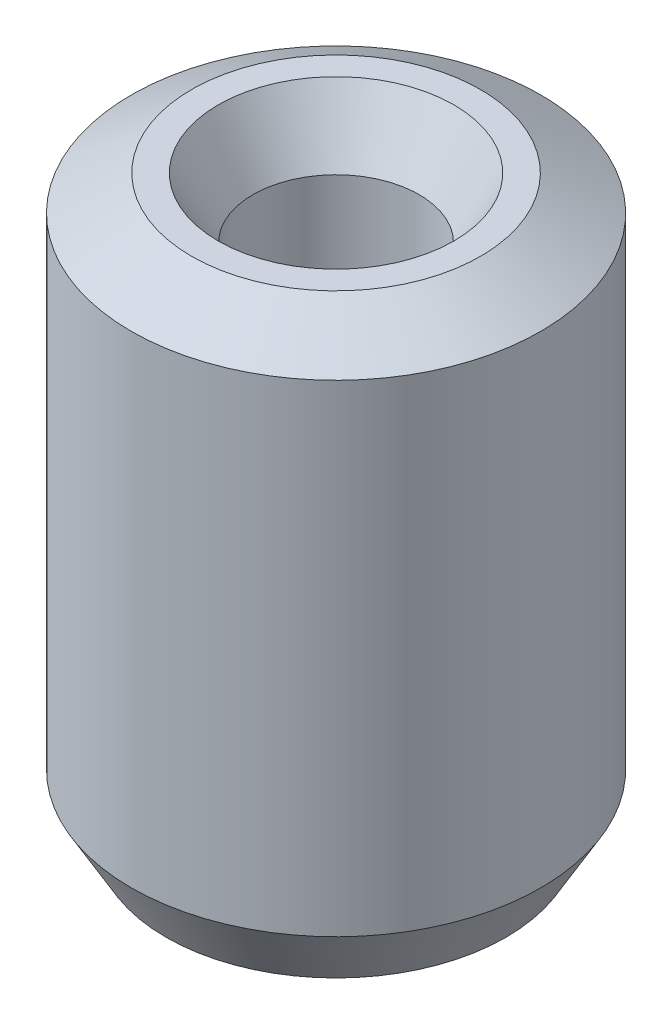
SolidWorks part; units mm, degrees
ref_plane "Front Plane" through (0, 0, 0) normal (0, 0, 1) x (1, 0, 0)
ref_plane "Top Plane" through (0, 0, 0) normal (0, 1, 0) x (1, 0, 0)
ref_plane "Right Plane" through (0, 0, 0) normal (1, 0, 0) x (0, 0, -1)
sketch "Sketch1" plane through (0, 0, 0) normal (0, 1, 0) x (1, 0, 0)
  circle A0 centre (0, 0) radius 17.5
  dimension "SLEEVE_OD" = 35
extrude "Boss-Extrude1" add sketch "Sketch1" along normal blind 49.3151
sketch "Sketch2" plane through (0, 0, 0) normal (0, 1, 0) x (1, 0, 0)
  circle A0 centre (0, 0) radius 7.101
  dimension "BORE_D" = 14.202
extrude "Cut-Extrude1" cut sketch "Sketch2" along normal through all
chamfer "Chamfer1" distance 2.9754 angle 60 4 edges at (0, 49.3151, 7.101) (0, 0, 7.101) (0, 0, 17.5) (0, 49.3151, 17.5) first distance on face at (0, 49.3151, 7.101) first distance on face at (0, 0, 7.101) first distance on face at (0, 49.3151, 17.5)
